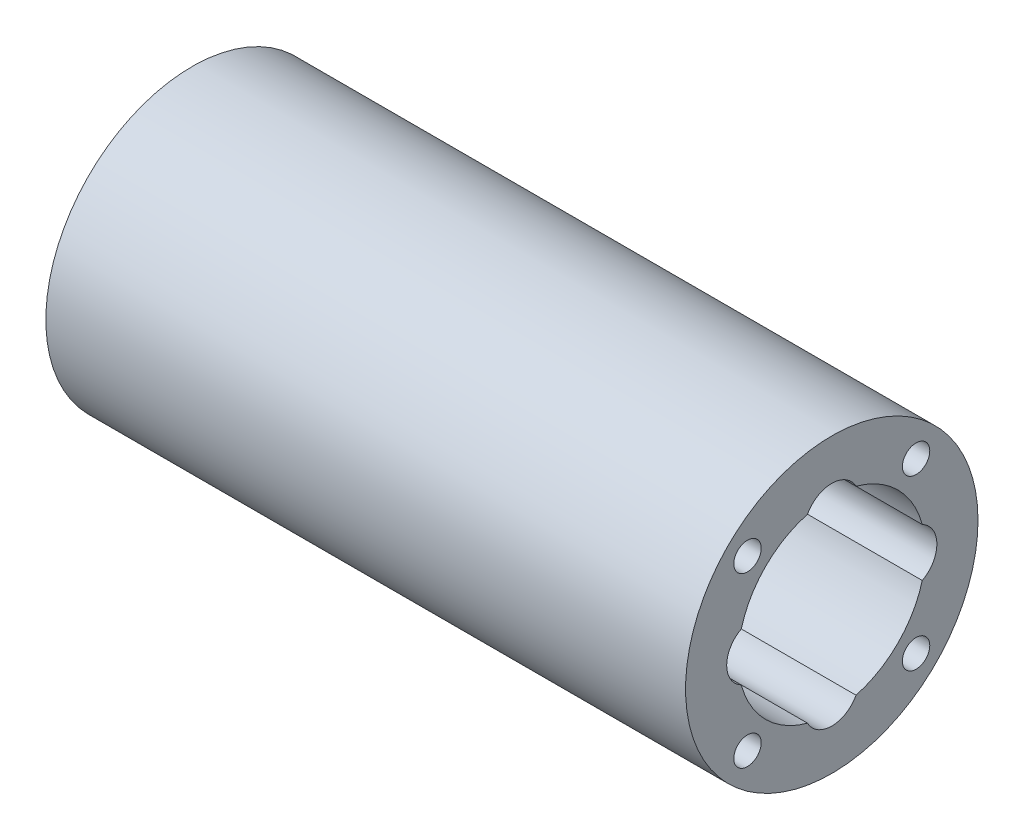
SolidWorks part; units mm, degrees
ref_plane "Front Plane" through (0, 0, 0) normal (0, 0, 1) x (1, 0, 0)
ref_plane "Top Plane" through (0, 0, 0) normal (0, 1, 0) x (1, 0, 0)
ref_plane "Right Plane" through (0, 0, 0) normal (1, 0, 0) x (0, 0, -1)
sketch "Sketch1" plane through (0, 0, 0) normal (1, 0, 0) x (0, 0, -1)
  circle A0 centre (0, 0) radius 10.25
  circle A2 centre (0, 8.5) radius 1.5
  circle A3 centre (0, -8.5) radius 1.5
  circle A4 centre (0, 0) radius 16
  circle A5 centre (0, 8.5) radius 3
  circle A6 centre (0, -8.5) radius 3
  circle A8 centre (0, 0) radius 5.25
  circle A9 centre (8.5, 0) radius 1.5
  circle A10 centre (8.5, 0) radius 3
  circle A11 centre (0, -8.5) radius 1.5
  circle A12 centre (0, -8.5) radius 3
  circle A13 centre (-8.5, 0) radius 1.5
  circle A14 centre (-8.5, 0) radius 3
  point P10 (0, 0)
  point P29 (0, 0)
  dimension "D1" = 20.5
  dimension "D2" = 32
  dimension "D3" = 3
  dimension "D7" = 10.5
  dimension "D5" = 1.5
  dimension "D6" = 1.5
  dimension "D4" = 2
  dimension "D8" = 4
extrude "Boss-Extrude2" add sketch "Sketch1" along normal blind 3 contours A4 A6 A0 A5 | A0 A5 | A0 A5 A2 | A0 A6 A3 | A0 A6 | A6 A0 A5 region at (0, 0, -5.472) region at (0, 9.2031, -2.8377) region at (0, 10.6911, 0) region at (0, -10.6911, 0) region at (0, -10.1735, 0) region at (0, 0, 15.5475)
extrude "Boss-Extrude4" add sketch "Sketch1<8>" against normal blind 10 contours A4 A6 A0 A5 region at (0, 0, 15.5475)
sketch "Sketch1<8>" plane through (0, 0, 0) normal (1, 0, 0) x (0, 0, -1) same geometry as "Sketch1"
extrude "Boss-Extrude6" add sketch "Sketch1<10>" along normal blind 3 contours A0 A10 | A0 A10 A9 | A0 A14 A13 | A0 A14 region at (0, -1.3279, -10.0864) region at (0, 0, -10.6911) region at (0, 2.5037, 6.9907) region at (0, 0, 10.6911)
sketch "Sketch1<10>" plane through (0, 0, 0) normal (1, 0, 0) x (0, 0, -1) same geometry as "Sketch1"
extrude "Boss-Extrude7" add sketch "Sketch1<11>" along normal blind 57 from surface contours A4 A14 A0 A5 A10 A6 region at (0, 0, 15.5475) starting at face at (3, 0, -16)
sketch "Sketch1<11>" plane through (0, 0, 0) normal (1, 0, 0) x (0, 0, -1) same geometry as "Sketch1"
sketch "Sketch2" plane through (-10, 0, 0) normal (-1, 0, 0) x (0, 0, 1)
  line L0 (0, 0) -> (-9.2228, 9.2228) construction
  circle A0 centre (0, 0) radius 10.25
  circle A1 centre (9.2228, 9.2228) radius 1.5
  circle A4 centre (-9.2228, 9.2228) radius 1.5
  circle A5 centre (9.2228, -9.2228) radius 1.5
  circle A6 centre (-9.2228, -9.2228) radius 1.5
  point P17 (0, 0)
  dimension "D1" = 13.043
  dimension "D2" = 3
  dimension "D3" = 4
extrude "Cut-Extrude2" cut sketch "Sketch2" along normal blind 5 from surface contours A1 | A4 | A6 | A5 region at (-10, 9.2228, 9.2228) region at (-10, 9.2228, -9.2228) region at (-10, -9.2228, 9.2228) region at (-10, -9.2228, -9.2228) starting at face at (60, 0, -16)
